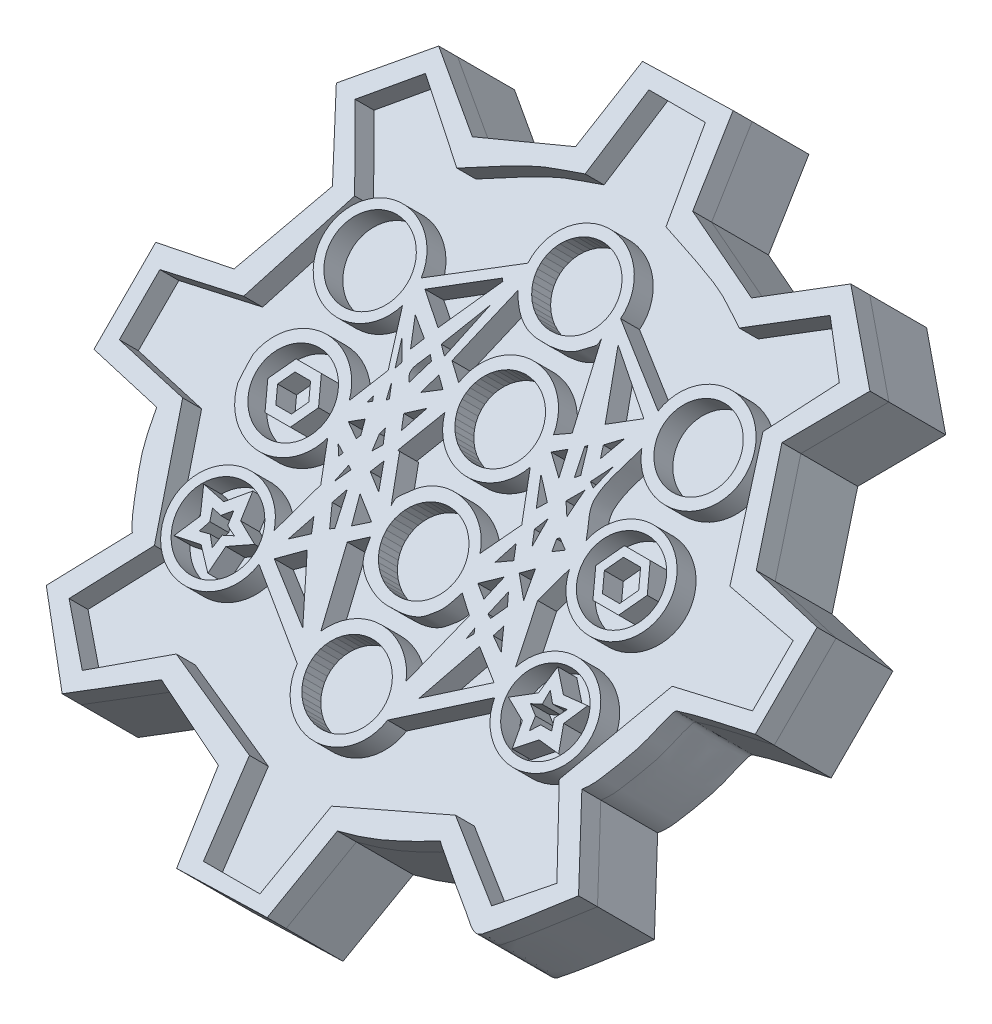
SolidWorks part; units mm, degrees
ref_plane "Front Plane" through (0, 0, 0) normal (0, 0, 1) x (1, 0, 0)
ref_plane "Top Plane" through (0, 0, 0) normal (0, 1, 0) x (1, 0, 0)
ref_plane "Right Plane" through (0, 0, 0) normal (1, 0, 0) x (0, 0, -1)
ref_plane "Plane2" through (0, -6.35, 0) normal (0, 1, 0) x (1, 0, 0)
sketch "Sketch2" plane through (0, -6.35, 0) normal (0, 1, 0) x (1, 0, 0)
  circle A0 centre (0, 0) radius 6.0325
  dimension "D1" = 12.065
ref_axis "Axis1" through (-6.2865, 0, 0) along (1, 0, 0)
ref_plane "Plane1" through (0, 0, 0) normal (0, 0.7071, 0.7071) x (1, 0, 0)
sketch "Sketch3" plane through (0, 0, 0) normal (0, 0.7071, 0.7071) x (1, 0, 0)
  line L0 (0, 0) -> (-25.4, 0) construction
  line L1 (-6.2865, 0) -> (6.2865, 0) construction
  line L2 (-25.4, -38.1) -> (-25.4, 38.1) construction
  circle A0 centre (0, 0) radius 12.7
  point P13 (-25.4, 0)
  point P15 (-20.32, 7.62)
  point P16 (-20.32, -7.62)
  point P17 (-20.32, -22.86)
  dimension "D1" = 25.4
  dimension "D4" = 25.4
  dimension "D5" = 76.2
extrude "Boss-Extrude1" add sketch "Sketch3" along normal blind 4.7625
extrude "Boss-Extrude2" add sketch "Sketch2" along normal up to surface and the other way blind 3.175 up to face at (0, -8.9803, 8.9803)
sketch "Sketch5" plane through (0, 3.3676, 3.3676) normal (0, 0.7071, 0.7071) x (1, 0, 0)
  line L0 (2.1384, 9.1764) -> (2.1514, 9.4647)
  line L1 (2.1514, 9.4647) -> (2.125, 9.7523)
  line L2 (2.125, 9.7523) -> (2.0598, 10.0341)
  line L3 (2.0598, 10.0341) -> (1.9568, 10.3051)
  line L4 (1.9568, 10.3051) -> (1.818, 10.5603)
  line L5 (1.818, 10.5603) -> (1.6457, 10.7953)
  line L6 (1.6457, 10.7953) -> (1.4431, 11.0059)
  line L7 (1.4431, 11.0059) -> (1.2138, 11.1882)
  line L8 (1.2138, 11.1882) -> (0.9619, 11.3391)
  line L9 (0.9619, 11.3391) -> (0.6918, 11.4559)
  line L10 (0.6918, 11.4559) -> (0.4085, 11.5365)
  line L11 (0.4085, 11.5365) -> (0.1168, 11.5794)
  line L12 (0.1168, 11.5794) -> (-0.1778, 11.5838)
  line L13 (-0.1778, 11.5838) -> (-0.4703, 11.5498)
  line L14 (-0.4703, 11.5498) -> (-0.7553, 11.4779)
  line L15 (-0.7553, 11.4779) -> (-1.0279, 11.3693)
  line L16 (-1.0279, 11.3693) -> (-1.283, 11.2261)
  line L17 (-1.283, 11.2261) -> (-1.5162, 11.0507)
  line L18 (-1.5162, 11.0507) -> (-1.7233, 10.8463)
  line L19 (-1.7233, 10.8463) -> (-1.9007, 10.6166)
  line L20 (-1.9007, 10.6166) -> (-2.045, 10.3657)
  line L21 (-2.045, 10.3657) -> (-2.1539, 10.098)
  line L22 (-2.1539, 10.098) -> (-2.2253, 9.8183)
  line L23 (-2.2253, 9.8183) -> (-2.2579, 9.5315)
  line L24 (-2.2579, 9.5315) -> (-2.2512, 9.243)
  line L25 (-2.2512, 9.243) -> (-2.2053, 8.9576)
  line L26 (-2.2053, 8.9576) -> (-2.121, 8.6806)
  line L27 (-2.121, 8.6806) -> (-1.9998, 8.417)
  line L28 (-1.9998, 8.417) -> (-1.8439, 8.1713)
  line L29 (-1.8439, 8.1713) -> (-1.6561, 7.948)
  line L30 (-1.6561, 7.948) -> (-1.4396, 7.7511)
  line L31 (-1.4396, 7.7511) -> (-1.1985, 7.5841)
  line L32 (-1.1985, 7.5841) -> (-0.9369, 7.45)
  line L33 (-0.9369, 7.45) -> (-0.6596, 7.3511)
  line L34 (-0.6596, 7.3511) -> (-0.3714, 7.2892)
  line L35 (-0.3714, 7.2892) -> (-0.0776, 7.2655)
  line L36 (-0.0776, 7.2655) -> (0.2166, 7.2803)
  line L37 (0.2166, 7.2803) -> (0.506, 7.3334)
  line L38 (0.506, 7.3334) -> (0.7854, 7.4239)
  line L39 (0.7854, 7.4239) -> (1.0498, 7.55)
  line L40 (1.0498, 7.55) -> (1.2946, 7.7097)
  line L41 (1.2946, 7.7097) -> (1.5152, 7.9)
  line L42 (1.5152, 7.9) -> (1.7079, 8.1175)
  line L43 (1.7079, 8.1175) -> (1.8691, 8.3584)
  line L44 (1.8691, 8.3584) -> (1.996, 8.6183)
  line L45 (1.996, 8.6183) -> (2.0863, 8.8926)
  line L46 (2.0863, 8.8926) -> (2.1384, 9.1764)
  line L47 (2.1553, 2.9225) -> (2.146, 3.2114)
  line L48 (2.146, 3.2114) -> (2.0975, 3.4967)
  line L49 (2.0975, 3.4967) -> (2.0105, 3.7731)
  line L50 (2.0105, 3.7731) -> (1.8868, 4.0357)
  line L51 (1.8868, 4.0357) -> (1.7284, 4.2799)
  line L52 (1.7284, 4.2799) -> (1.5383, 4.5013)
  line L53 (1.5383, 4.5013) -> (1.3198, 4.696)
  line L54 (1.3198, 4.696) -> (1.0768, 4.8604)
  line L55 (1.0768, 4.8604) -> (0.8136, 4.9916)
  line L56 (0.8136, 4.9916) -> (0.535, 5.0874)
  line L57 (0.535, 5.0874) -> (0.2459, 5.1459)
  line L58 (0.2459, 5.1459) -> (-0.0486, 5.1662)
  line L59 (-0.0486, 5.1662) -> (-0.3431, 5.1478)
  line L60 (-0.3431, 5.1478) -> (-0.6324, 5.0912)
  line L61 (-0.6324, 5.0912) -> (-0.9114, 4.9973)
  line L62 (-0.9114, 4.9973) -> (-1.1751, 4.8677)
  line L63 (-1.1751, 4.8677) -> (-1.4187, 4.7049)
  line L64 (-1.4187, 4.7049) -> (-1.638, 4.5117)
  line L65 (-1.638, 4.5117) -> (-1.8289, 4.2915)
  line L66 (-1.8289, 4.2915) -> (-1.9882, 4.0484)
  line L67 (-1.9882, 4.0484) -> (-2.1129, 3.7865)
  line L68 (-2.1129, 3.7865) -> (-2.2009, 3.5107)
  line L69 (-2.2009, 3.5107) -> (-2.2505, 3.2258)
  line L70 (-2.2505, 3.2258) -> (-2.2609, 2.9369)
  line L71 (-2.2609, 2.9369) -> (-2.2319, 2.6491)
  line L72 (-2.2319, 2.6491) -> (-2.164, 2.3677)
  line L73 (-2.164, 2.3677) -> (-2.0585, 2.0975)
  line L74 (-2.0585, 2.0975) -> (-1.9171, 1.8436)
  line L75 (-1.9171, 1.8436) -> (-1.7425, 1.6102)
  line L76 (-1.7425, 1.6102) -> (-1.5377, 1.4017)
  line L77 (-1.5377, 1.4017) -> (-1.3064, 1.2218)
  line L78 (-1.3064, 1.2218) -> (-1.0527, 1.0737)
  line L79 (-1.0527, 1.0737) -> (-0.7812, 0.9599)
  line L80 (-0.7812, 0.9599) -> (-0.4967, 0.8826)
  line L81 (-0.4967, 0.8826) -> (-0.2043, 0.8431)
  line L82 (-0.2043, 0.8431) -> (0.0908, 0.8421)
  line L83 (0.0908, 0.8421) -> (0.3834, 0.8797)
  line L84 (0.3834, 0.8797) -> (0.6682, 0.9552)
  line L85 (0.6682, 0.9552) -> (0.9401, 1.0671)
  line L86 (0.9401, 1.0671) -> (1.1944, 1.2137)
  line L87 (1.1944, 1.2137) -> (1.4263, 1.3921)
  line L88 (1.4263, 1.3921) -> (1.6319, 1.5992)
  line L89 (1.6319, 1.5992) -> (1.8074, 1.8314)
  line L90 (1.8074, 1.8314) -> (1.9497, 2.0845)
  line L91 (1.9497, 2.0845) -> (2.0563, 2.3539)
  line L92 (2.0563, 2.3539) -> (2.1252, 2.6349)
  line L93 (2.1252, 2.6349) -> (2.1553, 2.9225)
  line L94 (2.1447, -3.5357) -> (2.1432, -3.2468)
  line L95 (2.1432, -3.2468) -> (2.1025, -2.9605)
  line L96 (2.1025, -2.9605) -> (2.0232, -2.682)
  line L97 (2.0232, -2.682) -> (1.9066, -2.4162)
  line L98 (1.9066, -2.4162) -> (1.755, -2.1679)
  line L99 (1.755, -2.1679) -> (1.571, -1.9415)
  line L100 (1.571, -1.9415) -> (1.3579, -1.7411)
  line L101 (1.3579, -1.7411) -> (1.1195, -1.5702)
  line L102 (1.1195, -1.5702) -> (0.8601, -1.4319)
  line L103 (0.8601, -1.4319) -> (0.5842, -1.3286)
  line L104 (0.5842, -1.3286) -> (0.2968, -1.2622)
  line L105 (0.2968, -1.2622) -> (0.003, -1.2339)
  line L106 (0.003, -1.2339) -> (-0.2918, -1.2442)
  line L107 (-0.2918, -1.2442) -> (-0.5826, -1.2929)
  line L108 (-0.5826, -1.2929) -> (-0.864, -1.3791)
  line L109 (-0.864, -1.3791) -> (-1.1311, -1.5013)
  line L110 (-1.1311, -1.5013) -> (-1.379, -1.6573)
  line L111 (-1.379, -1.6573) -> (-1.6034, -1.8443)
  line L112 (-1.6034, -1.8443) -> (-1.8003, -2.059)
  line L113 (-1.8003, -2.059) -> (-1.9662, -2.2976)
  line L114 (-1.9662, -2.2976) -> (-2.098, -2.5558)
  line L115 (-2.098, -2.5558) -> (-2.1934, -2.8289)
  line L116 (-2.1934, -2.8289) -> (-2.2508, -3.1122)
  line L117 (-2.2508, -3.1122) -> (-2.2691, -3.4006)
  line L118 (-2.2691, -3.4006) -> (-2.248, -3.6888)
  line L119 (-2.248, -3.6888) -> (-2.1878, -3.9719)
  line L120 (-2.1878, -3.9719) -> (-2.0896, -4.2446)
  line L121 (-2.0896, -4.2446) -> (-1.9553, -4.5022)
  line L122 (-1.9553, -4.5022) -> (-1.7871, -4.7401)
  line L123 (-1.7871, -4.7401) -> (-1.5881, -4.954)
  line L124 (-1.5881, -4.954) -> (-1.3618, -5.1401)
  line L125 (-1.3618, -5.1401) -> (-1.1123, -5.295)
  line L126 (-1.1123, -5.295) -> (-0.8441, -5.4161)
  line L127 (-0.8441, -5.4161) -> (-0.5618, -5.5011)
  line L128 (-0.5618, -5.5011) -> (-0.2706, -5.5485)
  line L129 (-0.2706, -5.5485) -> (0.0244, -5.5576)
  line L130 (0.0244, -5.5576) -> (0.3179, -5.528)
  line L131 (0.3179, -5.528) -> (0.6046, -5.4604)
  line L132 (0.6046, -5.4604) -> (0.8794, -5.356)
  line L133 (0.8794, -5.356) -> (1.1375, -5.2166)
  line L134 (1.1375, -5.2166) -> (1.3742, -5.0447)
  line L135 (1.3742, -5.0447) -> (1.5854, -4.8434)
  line L136 (1.5854, -4.8434) -> (1.7671, -4.6162)
  line L137 (1.7671, -4.6162) -> (1.9163, -4.3673)
  line L138 (1.9163, -4.3673) -> (2.0302, -4.101)
  line L139 (2.0302, -4.101) -> (2.1067, -3.8222)
  line L140 (2.1067, -3.8222) -> (2.1447, -3.5357)
  line L141 (2.1098, -10.2575) -> (2.1477, -9.9761)
  line L142 (2.1477, -9.9761) -> (2.1479, -9.692)
  line L143 (2.1479, -9.692) -> (2.1103, -9.41)
  line L144 (2.1103, -9.41) -> (2.0357, -9.135)
  line L145 (2.0357, -9.135) -> (1.9252, -8.8716)
  line L146 (1.9252, -8.8716) -> (1.7807, -8.6245)
  line L147 (1.7807, -8.6245) -> (1.6048, -8.3977)
  line L148 (1.6048, -8.3977) -> (1.4005, -8.1951)
  line L149 (1.4005, -8.1951) -> (1.1711, -8.0204)
  line L150 (1.1711, -8.0204) -> (0.9208, -7.8763)
  line L151 (0.9208, -7.8763) -> (0.6537, -7.7655)
  line L152 (0.6537, -7.7655) -> (0.3744, -7.6897)
  line L153 (0.3744, -7.6897) -> (0.0877, -7.6504)
  line L154 (0.0877, -7.6504) -> (-0.2014, -7.6481)
  line L155 (-0.2014, -7.6481) -> (-0.4882, -7.6829)
  line L156 (-0.4882, -7.6829) -> (-0.7675, -7.7542)
  line L157 (-0.7675, -7.7542) -> (-1.0348, -7.8608)
  line L158 (-1.0348, -7.8608) -> (-1.2853, -8.0008)
  line L159 (-1.2853, -8.0008) -> (-1.5148, -8.172)
  line L160 (-1.5148, -8.172) -> (-1.7194, -8.3712)
  line L161 (-1.7194, -8.3712) -> (-1.8956, -8.5952)
  line L162 (-1.8956, -8.5952) -> (-2.0403, -8.8401)
  line L163 (-2.0403, -8.8401) -> (-2.1511, -9.1017)
  line L164 (-2.1511, -9.1017) -> (-2.2262, -9.3755)
  line L165 (-2.2262, -9.3755) -> (-2.2641, -9.6569)
  line L166 (-2.2641, -9.6569) -> (-2.2642, -9.941)
  line L167 (-2.2642, -9.941) -> (-2.2267, -10.223)
  line L168 (-2.2267, -10.223) -> (-2.152, -10.498)
  line L169 (-2.152, -10.498) -> (-2.0415, -10.7613)
  line L170 (-2.0415, -10.7613) -> (-1.897, -11.0085)
  line L171 (-1.897, -11.0085) -> (-1.7211, -11.2353)
  line L172 (-1.7211, -11.2353) -> (-1.5168, -11.4378)
  line L173 (-1.5168, -11.4378) -> (-1.2875, -11.6126)
  line L174 (-1.2875, -11.6126) -> (-1.0371, -11.7567)
  line L175 (-1.0371, -11.7567) -> (-0.77, -11.8675)
  line L176 (-0.77, -11.8675) -> (-0.4907, -11.9433)
  line L177 (-0.4907, -11.9433) -> (-0.2041, -11.9826)
  line L178 (-0.2041, -11.9826) -> (0.0851, -11.9849)
  line L179 (0.0851, -11.9849) -> (0.3718, -11.9501)
  line L180 (0.3718, -11.9501) -> (0.6512, -11.8788)
  line L181 (0.6512, -11.8788) -> (0.9184, -11.7722)
  line L182 (0.9184, -11.7722) -> (1.169, -11.6321)
  line L183 (1.169, -11.6321) -> (1.3985, -11.461)
  line L184 (1.3985, -11.461) -> (1.6031, -11.2618)
  line L185 (1.6031, -11.2618) -> (1.7793, -11.0378)
  line L186 (1.7793, -11.0378) -> (1.924, -10.7929)
  line L187 (1.924, -10.7929) -> (2.0348, -10.5313)
  line L188 (2.0348, -10.5313) -> (2.1098, -10.2575)
  line L189 (11.1815, -5.5544) -> (9.8248, -5.6673)
  line L190 (9.1225, -5.7799) -> (9.1225, -6.4565)
  line L191 (9.1225, -6.4565) -> (8.5826, -6.6798)
  line L192 (8.5826, -6.6798) -> (9.1225, -7.0175)
  line L193 (9.1225, -7.0175) -> (9.2346, -7.6897)
  line L194 (9.2346, -7.6897) -> (9.5792, -7.2361)
  line L195 (9.5792, -7.2361) -> (10.233, -7.2361)
  line L196 (10.233, -7.2361) -> (10.011, -6.6996)
  line L197 (10.011, -6.6996) -> (10.3747, -6.1182)
  line L198 (10.3747, -6.1182) -> (9.5792, -6.227)
  line L199 (9.5792, -6.227) -> (9.1225, -5.7799)
  line L200 (10.5709, -6.6996) -> (11.1815, -5.5544)
  line L201 (11.1233, -7.9115) -> (10.5709, -6.6996)
  line L202 (9.9061, -7.8107) -> (11.1233, -7.9115)
  line L203 (8.9329, -8.7049) -> (9.9061, -7.8107)
  line L204 (8.6664, -7.4675) -> (8.9329, -8.7049)
  line L205 (7.4397, -6.9096) -> (8.6664, -7.4675)
  line L206 (8.6664, -6.1182) -> (7.4397, -6.9096)
  line L207 (8.8526, -4.7674) -> (8.6664, -6.1182)
  line L208 (9.8248, -5.6673) -> (8.8526, -4.7674)
  line L209 (7.9446, -0.3005) -> (8.7074, -1.6217)
  line L210 (10.4872, -0.3005) -> (9.9787, 0.5803)
  line L211 (9.9787, 0.5803) -> (8.9617, 0.5803)
  line L212 (8.9617, 0.5803) -> (8.4532, -0.3005)
  line L213 (8.4532, -0.3005) -> (8.9617, -1.1812)
  line L214 (8.9617, -1.1812) -> (9.9787, -1.1812)
  line L215 (9.9787, -1.1812) -> (10.4872, -0.3005)
  line L216 (8.7074, 1.0207) -> (7.9446, -0.3005)
  line L217 (10.233, 1.0207) -> (8.7074, 1.0207)
  line L218 (10.9958, -0.3005) -> (10.233, 1.0207)
  line L219 (10.233, -1.6217) -> (10.9958, -0.3005)
  line L220 (8.7074, -1.6217) -> (10.233, -1.6217)
  line L221 (-11.4271, -0.3799) -> (-10.6764, -1.6802)
  line L222 (-9.0014, -0.3799) -> (-9.4635, 0.4205)
  line L223 (-9.4635, 0.4205) -> (-10.3877, 0.4205)
  line L224 (-10.3877, 0.4205) -> (-10.8498, -0.3799)
  line L225 (-10.8498, -0.3799) -> (-10.3877, -1.1803)
  line L226 (-10.3877, -1.1803) -> (-9.4635, -1.1803)
  line L227 (-9.4635, -1.1803) -> (-9.0014, -0.3799)
  line L228 (-10.6764, 0.9204) -> (-11.4271, -0.3799)
  line L229 (-9.1749, 0.9204) -> (-10.6764, 0.9204)
  line L230 (-8.4241, -0.3799) -> (-9.1749, 0.9204)
  line L231 (-9.1749, -1.6802) -> (-8.4241, -0.3799)
  line L232 (-10.6764, -1.6802) -> (-9.1749, -1.6802)
  line L233 (-9.9942, -7.2361) -> (-10.5615, -7.3583)
  line L234 (-11.5651, -5.5544) -> (-10.2232, -5.7799)
  line L235 (-10.2232, -5.7799) -> (-9.2055, -4.7798)
  line L236 (-9.2055, -4.7798) -> (-8.9824, -6.1183)
  line L237 (-8.9824, -6.1183) -> (-7.7542, -6.6768)
  line L238 (-7.7542, -6.6768) -> (-8.9824, -7.3583)
  line L239 (-8.9824, -7.3583) -> (-9.0939, -8.7049)
  line L240 (-9.0939, -8.7049) -> (-10.1253, -7.8107)
  line L241 (-10.1253, -7.8107) -> (-11.5651, -8.0507)
  line L242 (-11.5651, -8.0507) -> (-10.8942, -6.7924)
  line L243 (-10.8942, -6.7924) -> (-11.5651, -5.5544)
  line L244 (-9.5485, -7.6897) -> (-9.9942, -7.2361)
  line L245 (-9.4371, -7.0269) -> (-9.5485, -7.6897)
  line L246 (-8.8749, -6.7924) -> (-9.4371, -7.0269)
  line L247 (-9.4371, -6.5611) -> (-8.8749, -6.7924)
  line L248 (-9.5485, -5.8929) -> (-9.4371, -6.5611)
  line L249 (-10.0073, -6.3437) -> (-9.5485, -5.8929)
  line L250 (-10.5615, -6.2297) -> (-10.0073, -6.3437)
  line L251 (-10.3287, -6.7924) -> (-10.5615, -6.2297)
  line L252 (-10.5615, -7.3583) -> (-10.3287, -6.7924)
  line L253 (2.5066, 1.9018) -> (3.6134, -0.3799)
  line L254 (3.6134, -4.7674) -> (2.4884, -8.4799)
  line L255 (-3.6991, 4.1201) -> (-2.8364, 3.4604)
  line L256 (6.2009, 3.6701) -> (5.555, 2.634)
  line L257 (-6.5116, 3.8951) -> (-6.033, 2.6576)
  line L258 (5.5259, 2.2076) -> (4.9634, 1.4201)
  line L259 (-3.4238, 6.9255) -> (-4.5991, 4.493)
  line L260 (-3.4741, 8.0576) -> (-5.1616, 5.0201)
  line L261 (3.2759, 8.1701) -> (6.3134, 6.0326)
  line L262 (-6.5116, 5.0201) -> (-5.4991, 4.3451)
  line L263 (4.9634, 2.6576) -> (4.7384, 2.4326)
  line L264 (-3.9241, 3.3326) -> (-3.3616, 2.8826)
  line L265 (3.7259, 3.3326) -> (4.0634, 2.0951)
  line L266 (-5.8366, 2.0951) -> (-5.4991, 1.4201)
  line L267 (-3.5866, 1.8701) -> (-4.1491, 0.5201)
  line L268 (3.1634, 1.8701) -> (4.1759, 0.9701)
  line L269 (-6.2866, 1.1951) -> (-6.1741, 0.9701)
  line L270 (4.6259, 0.4076) -> (4.6259, -0.9424)
  line L271 (-4.5991, -0.3799) -> (-4.9366, -0.8299)
  line L272 (-5.8366, -0.4924) -> (-5.9491, -0.7174)
  line L273 (6.2009, -0.3799) -> (5.6384, -0.7174)
  line L274 (-4.1491, -0.9424) -> (-3.5866, -2.1799)
  line L275 (3.8384, -1.1674) -> (4.1759, -1.8424)
  line L276 (-6.6241, -1.2799) -> (-6.1741, -1.5049)
  line L277 (-5.6116, -1.8424) -> (-5.3866, -1.9549)
  line L278 (-4.3741, -2.6299) -> (-3.1366, -3.4174)
  line L279 (4.1759, -2.6299) -> (3.8384, -3.8674)
  line L280 (-4.5991, -4.4299) -> (-4.8241, -4.5424)
  line L281 (5.0759, -3.6424) -> (4.6259, -4.4299)
  line L282 (-5.8366, -4.4299) -> (-5.4991, -5.1049)
  line L283 (5.4134, -4.4299) -> (5.9759, -5.4424)
  line L284 (4.8509, -5.6674) -> (6.4259, -6.6799)
  line L285 (-5.2741, -5.7799) -> (-3.4741, -8.7049)
  line L286 (4.7384, -2.1799) -> (5.347, -1.6823)
  line L287 (-4.8241, 3.8951) -> (-4.5991, 3.6701)
  line L288 (2.7134, -4.0924) -> (3.6134, -4.7674)
  line L289 (-3.6991, -4.6549) -> (-2.7991, -3.9799)
  line L290 (-2.585, -8.443) -> (-3.6991, -4.6549)
  line L291 (3.5009, 4.0076) -> (2.7134, 3.5576)
  line L292 (2.3759, 8.0576) -> (3.5009, 4.0076)
  line L293 (-3.6991, 4.1201) -> (-2.5741, 8.0576)
  line L294 (5.555, 2.634) -> (5.8506, 2.4498)
  line L295 (5.8506, 2.4498) -> (6.2009, 3.6701)
  line L296 (-5.8854, 3.002) -> (-6.5116, 3.8951)
  line L297 (4.9634, 1.4201) -> (5.4134, 0.8576)
  line L298 (5.4134, 0.8576) -> (5.5259, 2.2076)
  line L299 (-4.5991, 4.493) -> (-4.1491, 4.1201)
  line L300 (-4.1491, 4.1201) -> (-3.4238, 6.9255)
  line L301 (-3.5866, 8.1701) -> (-3.4741, 8.0576)
  line L302 (-6.7366, 6.1451) -> (-3.5866, 8.1701)
  line L303 (-5.1616, 5.0201) -> (-6.7366, 6.1451)
  line L304 (4.7384, 5.0201) -> (3.2759, 8.1701)
  line L305 (6.3134, 6.0326) -> (4.7384, 5.0201)
  line L306 (-5.8366, 3.6701) -> (-6.5116, 5.0201)
  line L307 (-5.4991, 4.3451) -> (-5.8366, 3.6701)
  line L308 (5.1884, 4.2326) -> (5.9759, 4.9076)
  line L309 (5.4134, 3.6701) -> (5.1884, 4.2326)
  line L310 (4.5134, 3.8951) -> (4.9634, 2.6576)
  line L311 (4.4009, 3.7826) -> (4.5134, 3.8951)
  line L312 (4.7384, 2.4326) -> (4.4009, 3.7826)
  line L313 (-4.2616, 2.3201) -> (-3.9241, 3.3326)
  line L314 (-3.3616, 2.8826) -> (-4.2616, 2.3201)
  line L315 (3.0509, 2.8826) -> (3.7259, 3.3326)
  line L316 (4.0634, 2.0951) -> (3.0509, 2.8826)
  line L317 (-5.6116, 1.3076) -> (-5.8366, 2.0951)
  line L318 (-5.4991, 1.4201) -> (-5.6116, 1.3076)
  line L319 (-4.4866, 1.1951) -> (-3.5866, 1.8701)
  line L320 (-4.1491, 0.5201) -> (-4.4866, 1.1951)
  line L321 (3.8384, 0.5201) -> (3.1634, 1.8701)
  line L322 (4.1759, 0.9701) -> (3.8384, 0.5201)
  line L323 (-6.3991, 0.8576) -> (-6.2866, 1.1951)
  line L324 (-6.1741, 0.9701) -> (-6.3991, 0.8576)
  line L325 (4.2884, -0.2674) -> (4.6259, 0.4076)
  line L326 (4.6259, -0.9424) -> (4.2884, -0.2674)
  line L327 (-4.9366, 0.2951) -> (-4.5991, -0.3799)
  line L328 (-5.0491, -0.0424) -> (-4.9366, 0.2951)
  line L329 (-4.9366, -0.8299) -> (-5.0491, -0.0424)
  line L330 (-6.0616, 0.1826) -> (-5.8366, -0.4924)
  line L331 (-6.7366, -0.2674) -> (-6.0616, 0.1826)
  line L332 (-5.9491, -0.7174) -> (-6.7366, -0.2674)
  line L333 (5.6384, -0.0424) -> (6.2009, -0.3799)
  line L334 (5.5259, -0.1549) -> (5.6384, -0.0424)
  line L335 (5.6384, -0.7174) -> (5.5259, -0.1549)
  line L336 (-4.4866, -1.6174) -> (-4.1491, -0.9424)
  line L337 (-3.5866, -2.1799) -> (-4.4866, -1.6174)
  line L338 (3.3884, -2.2924) -> (3.8384, -1.1674)
  line L339 (4.1759, -1.8424) -> (3.3884, -2.2924)
  line L340 (-6.2866, -1.7299) -> (-6.6241, -1.2799)
  line L341 (-6.1741, -1.5049) -> (-6.2866, -1.7299)
  line L342 (-5.8366, -2.7424) -> (-5.6116, -1.8424)
  line L343 (-5.3866, -1.9549) -> (-5.8366, -2.7424)
  line L344 (-3.9241, -3.9799) -> (-4.3741, -2.6299)
  line L345 (-3.1366, -3.4174) -> (-3.9241, -3.9799)
  line L346 (3.1634, -3.4174) -> (4.1759, -2.6299)
  line L347 (3.8384, -3.8674) -> (3.1634, -3.4174)
  line L348 (-5.0491, -2.7424) -> (-4.5991, -4.4299)
  line L349 (-5.3866, -3.5299) -> (-5.0491, -2.7424)
  line L350 (-4.8241, -4.5424) -> (-5.3866, -3.5299)
  line L351 (4.7384, -3.0799) -> (5.0759, -3.6424)
  line L352 (4.4009, -4.3174) -> (4.7384, -3.0799)
  line L353 (4.6259, -4.4299) -> (4.4009, -4.3174)
  line L354 (-6.3991, -5.7799) -> (-5.8366, -4.4299)
  line L355 (-5.4991, -5.1049) -> (-6.3991, -5.7799)
  line L356 (5.1884, -4.9924) -> (5.4134, -4.4299)
  line L357 (5.9759, -5.4424) -> (5.1884, -4.9924)
  line L358 (4.0634, -5.6674) -> (4.1759, -5.1049)
  line L359 (4.2884, -5.3299) -> (4.0634, -5.6674)
  line L360 (3.5009, -8.8174) -> (4.8509, -5.6674)
  line L361 (6.4259, -6.6799) -> (3.5009, -8.8174)
  line L362 (-6.5116, -6.7924) -> (-5.2741, -5.7799)
  line L363 (-3.4741, -8.7049) -> (-6.5116, -6.7924)
  line L364 (5.6384, -3.0799) -> (4.7384, -2.1799)
  line L365 (5.347, -1.6823) -> (5.6384, -3.0799)
  line L366 (6.9884, -5.6673) -> (6.2574, -2.7867)
  line L367 (6.843, -7.2114) -> (2.6619, -10.2672)
  line L368 (-2.7991, -10.1154) -> (-7.0549, -7.3059)
  line L369 (-7.2401, -5.7799) -> (-6.3459, -3.1325)
  line L370 (-6.3459, -3.1325) -> (-7.2401, -1.2799)
  line L371 (-7.2401, 0.5201) -> (-6.2866, 2.4327)
  line L372 (-7.3159, 5.094) -> (-6.2866, 2.4327)
  line L373 (-7.1866, 6.4748) -> (-2.827, 9.2491)
  line L374 (2.7134, 9.1764) -> (6.751, 6.6092)
  line L375 (-4.5991, 3.6701) -> (-5.0491, 2.4326)
  line L376 (-3.8116, -0.2674) -> (-2.6866, 2.0951)
  line L377 (-3.6991, -0.2674) -> (-3.8116, -0.2674)
  line L378 (-2.6866, -2.4049) -> (-3.6991, -0.2674)
  line L379 (3.6134, -0.3799) -> (2.4884, -2.2924)
  line L380 (5.9759, 4.9076) -> (5.4134, 3.6701)
  line L381 (4.1759, -5.1049) -> (4.2884, -5.3299)
  line L382 (6.2574, -2.7867) -> (6.868, -0.979)
  line L383 (-6.033, 2.6576) -> (-5.8854, 3.002)
  line L384 (-12.2491, 8.0576) -> (-14.6116, 2.0951)
  line L385 (-19.014, 1.3076) -> (-14.6116, 2.0951)
  line L386 (-12.1792, -8.8174) -> (-14.7114, -2.8713)
  line L387 (-12.1792, -14.8613) -> (-14.6116, -12.5299)
  line L388 (-14.7114, 11.5722) -> (-12.2491, 8.0576)
  line L389 (-8.4241, -12.2962) -> (-2.5741, -14.4424)
  line L390 (-1.8991, -19.2478) -> (-2.5741, -14.4424)
  line L391 (-1.8991, -19.2478) -> (1.4449, -19.2478)
  line L392 (1.4449, -19.2478) -> (2.3759, -14.5643)
  line L393 (-19.014, -2.0891) -> (-14.7114, -2.8713)
  line L394 (8.1134, -12.2962) -> (12.0509, -14.8312)
  line L395 (14.3676, -12.6424) -> (12.0509, -14.8312)
  line L396 (11.804, -8.8174) -> (14.3676, -12.6424)
  line L397 (-12.1792, -14.8613) -> (-8.4241, -12.2962)
  line L398 (18.6402, -2.2924) -> (14.4368, -3.0799)
  line L399 (18.6402, 1.1109) -> (18.6402, -2.2924)
  line L400 (14.4368, 1.7576) -> (18.6402, 1.1109)
  line L401 (-19.014, -2.0891) -> (-19.014, 1.3076)
  line L402 (14.0759, 11.4326) -> (11.9384, 8.0576)
  line L403 (11.9384, 13.6826) -> (14.0759, 11.4326)
  line L404 (-14.6116, -12.5299) -> (-12.1792, -8.8174)
  line L405 (1.4449, 18.0701) -> (2.3759, 13.4576)
  line L406 (-1.8991, 18.0701) -> (1.4449, 18.0701)
  line L407 (-2.5741, 13.6826) -> (-1.8991, 18.0701)
  line L408 (-12.2491, 13.9853) -> (-8.4241, 11.2076)
  line L409 (2.3759, -19.9549) -> (3.2759, -15.3424)
  line L410 (2.3759, -19.9549) -> (-2.9116, -20.0674)
  line L411 (-3.6991, -15.4549) -> (-2.9116, -20.0674)
  line L412 (14.4368, -3.0799) -> (11.804, -8.8174)
  line L413 (-12.4741, -16.1299) -> (-8.4241, -13.5424)
  line L414 (-15.9616, -12.5299) -> (-12.4741, -16.1299)
  line L415 (-13.4866, -8.8174) -> (-15.9616, -12.5299)
  line L416 (-19.8991, -2.9674) -> (-15.6241, -3.7549)
  line L417 (-19.8991, -2.9674) -> (-19.8991, 2.2076)
  line L418 (-15.7366, 2.8826) -> (-19.8991, 2.2076)
  line L419 (-13.4866, 7.9451) -> (-15.7366, 2.8826)
  line L420 (-15.9616, 11.7701) -> (-13.4866, 7.9451)
  line L421 (-12.3616, 15.2576) -> (-15.9616, 11.7701)
  line L422 (-8.5366, 12.6701) -> (-12.3616, 15.2576)
  line L423 (-3.6991, 14.4701) -> (-8.5366, 12.6701)
  line L424 (-2.9116, 18.9701) -> (-3.6991, 14.4701)
  line L425 (2.3759, -14.5643) -> (8.1134, -12.2962)
  line L426 (3.1634, 14.5826) -> (2.3759, 19.0826)
  line L427 (8.0009, 12.6701) -> (3.1634, 14.5826)
  line L428 (12.0509, 15.2576) -> (8.0009, 12.6701)
  line L429 (15.6509, 11.7701) -> (12.0509, 15.2576)
  line L430 (13.0634, 8.0576) -> (15.6509, 11.7701)
  line L431 (15.2009, 2.8826) -> (13.0634, 8.0576)
  line L432 (19.3634, 2.0951) -> (15.2009, 2.8826)
  line L433 (19.3634, 2.0951) -> (19.3634, -3.0799)
  line L434 (15.6509, -12.6424) -> (13.0634, -8.7049)
  line L435 (8.2259, 11.3201) -> (11.9384, 13.6826)
  line L436 (-14.7114, 11.5722) -> (-12.2491, 13.9853)
  line L437 (11.9384, 8.0576) -> (14.4368, 1.7576)
  line L438 (-8.4241, -13.5424) -> (-3.6991, -15.4549)
  line L439 (-2.9116, 18.9701) -> (2.3759, 19.0826)
  circle A0 centre (9.4909, 6.1241) radius 2.1625
  circle A1 centre (-9.9256, -0.3799) radius 2.1919
  circle A2 centre (9.4702, -0.3005) radius 2.185
  circle A3 centre (-9.7958, -6.8643) radius 2.2672
  circle A4 centre (-9.9039, 6.0327) radius 2.2368
  circle A5 centre (9.4702, -6.6798) radius 2.1642
  arc A6 (2.4884, -8.4799) -> (-2.585, -8.443) centre (-0.0582, -9.8165) ccw
  arc A7 (2.7134, 3.5576) -> (-2.8364, 3.4604) centre (-0.0527, 3.002) ccw
  arc A8 (6.843, -7.2114) -> (6.9884, -5.6673) centre (9.4702, -6.6798) ccw
  arc A9 (-2.7991, -10.1154) -> (2.6619, -10.2672) centre (-0.0582, -9.8165) ccw
  arc A10 (-7.2401, -5.7799) -> (-7.0549, -7.3059) centre (-9.7958, -6.8643) ccw
  arc A11 (-7.2401, 0.5201) -> (-7.2401, -1.2799) centre (-9.9256, -0.3799) ccw
  arc A12 (-7.1866, 6.4748) -> (-7.3159, 5.094) centre (-9.9039, 6.0327) ccw
  arc A13 (2.7134, 9.1764) -> (-2.827, 9.2491) centre (-0.054, 9.426) ccw
  arc A14 (6.9884, 4.9077) -> (6.751, 6.6092) centre (9.4909, 6.1241) ccw
  arc A15 (6.868, -0.979) -> (6.8759, 0.4077) centre (9.4702, -0.3005) ccw
  arc A16 (-2.6866, 2.0951) -> (2.5066, 1.9018) centre (-0.0527, 3.002) ccw
  spline S0 degree 3 poles (-2.7991, -3.9799) (-2.7241, -4.2799) (-2.7021, -4.5984) (-2.5741, -4.8799) (-2.2447, -5.6045) (-1.0499, -6.1174) (-0.3241, -6.1174) (0.2812, -6.1174) (1.1746, -6.141) (1.7009, -5.6674) (2.4016, -5.0368) (2.372, -4.889) (2.7134, -4.0924) knots 0 0 0 0 1 1 1 2 2 2 3 3 3 4 4 4 4
  spline S1 degree 3 poles (-2.5741, 8.0576) (-2.1046, 7.3533) (-1.4724, 6.7846) (-0.5491, 6.7076) (0.0361, 6.6588) (1.1397, 6.6526) (1.7009, 7.1576) (2.4003, 7.7871) (2.3759, 7.6196) (2.3759, 8.0576) knots 0 0 0 0 1 1 1 2 2 2 3 3 3 3
  spline S2 degree 3 poles (6.8759, 0.4077) (6.6466, 0.9732) (6.1729, 1.4942) (6.1881, 2.1043) (6.2124, 3.0758) (6.7216, 3.9732) (6.9884, 4.9077) knots 0 0 0 0 1 1 1 2 2 2 2
  spline S3 degree 3 poles (-5.0491, 2.4326) (-5.5341, 2.9176) (-5.0848, 3.3086) (-4.8241, 3.8951) knots 0 0 0 0 1 1 1 1
  spline S4 degree 3 poles (2.4884, -2.2924) (1.7998, -0.5709) (-0.8003, 0.0518) (-2.1241, -1.3924) (-2.7065, -2.0277) (-2.6866, -1.97) (-2.6866, -2.4049) knots 0 0 0 0 1 1 1 2 2 2 2
  spline S5 degree 3 poles (8.1134, -13.5424) (8.1509, -13.5799) (8.1823, -13.6247) (8.2259, -13.6549) (9.106, -14.2642) (10.1409, -14.984) (11.0384, -15.5674) (11.335, -15.7602) (11.6028, -16.018) (11.9384, -16.1299) (12.0851, -16.1788) (12.2757, -16.1233) (12.3884, -16.0174) (13.5288, -14.9461) (14.5634, -13.7674) (15.6509, -12.6424) knots 0 0 0 0 1 1 1 2 2 2 3 3 3 4 4 4 5 5 5 5
  spline S6 degree 3 poles (2.3759, 13.4576) (3.6509, 13.0826) (4.9526, 12.7887) (6.2009, 12.3326) (6.9097, 12.0736) (7.5509, 11.6576) (8.2259, 11.3201) knots 0 0 0 0 1 1 1 2 2 2 2
  spline S7 degree 3 poles (-8.4241, 11.2076) (-7.2991, 11.7701) (-6.2075, 12.405) (-5.0491, 12.8951) (-4.2518, 13.2324) (-3.3991, 13.4201) (-2.5741, 13.6826) knots 0 0 0 0 1 1 1 2 2 2 2
  spline S8 degree 3 poles (3.2759, -15.3424) (5.2131, -14.9549) (6.3651, -14.4165) (8.1134, -13.5424) knots 0 0 0 0 1 1 1 1
  spline S9 degree 3 poles (-15.6241, -3.7549) (-15.432, -4.7154) (-15.1791, -5.7143) (-14.7241, -6.5674) (-14.6049, -6.791) (-13.9234, -8.3806) (-13.4866, -8.8174) knots 0 0 0 0 1 1 1 2 2 2 2
  spline S10 degree 3 poles (13.0634, -8.7049) (13.291, -8.4772) (13.4867, -8.1958) (13.6259, -7.9174) (13.941, -7.2872) (14.2676, -6.6604) (14.5259, -6.0049) (14.7563, -5.42) (14.8711, -4.7947) (15.0884, -4.2049) (15.1351, -4.078) (15.1826, -3.9018) (15.3134, -3.8674) (16.6434, -3.5174) (18.0134, -3.3424) (19.3634, -3.0799) knots 0 0 0 0 1 1 1 2 2 2 3 3 3 4 4 4 5 5 5 5
  circle M1 centre (0, 0) radius 12.7
extrude "Boss-Extrude3" add sketch "Sketch5" against normal blind 4.7625 contours L422 L421 L420 L419 L418 L417 L416 S9 L415 L414 L413 L438 L411 L410 L409 S8 S5 L434 S10 L433 L432 L431 L430 L429 L428 L427 L426 L439 L424 L423
extrude "Boss-Extrude4" add sketch "Sketch5<3>" along normal blind 1.5875 separate body contours A12 A4 M1 | A15 S2 A14 A0 L374 A13 L373 A12 A4 L372 L371 A11 L370 L369 A10 A3 L368 A9 L367 A8 A5 L366 L382 A2 A1 L383 L257 L296 L300 L299 L259 L298 M1 | L221 L232 L231 L230 L229 L228 L227 L226 L225 L224 L223 L222 | L434 S10 L433 L432 L431 L430 L429 L428 L427 L426 L439 L424 L423 L422 L421 L420 L419 L418 L417 L416 S9 L415 L414 L413 L438 L411 L410 L409 S8 S5 L408 S7 L407 L406 L405 S6 L435 L403 L402 L437 L400 L399 L398 L412 L396 L395 L394 L425 L392 L391 | L252 L251 L250 L249 L248 L247 L246 L245 L244 L233 L240 L239 L238 L237 L236 L235 L234 M1 | A10 A3 M1 | L189 L208 L207 L206 L205 L204 L203 L202 L201 L200 L199 L198 L197 L196 L195 L194 L193 L192 L191 L190 M1 | A8 A5 M1 | L209 L220 L219 L218 L217 L216 L215 L214 L213 L212 L211 L210 | A14 A0 M1 | L233 L252 L234 L243 L242 L241 L240 M1 | L202 L201 M1 region at (10.8283, -0.9468, 7.682) region at (10.6023, -1.9687, 8.7039) region at (11.5563, -0.4494, 7.1846) region at (7.4148, -0.3306, 7.0658) region at (-12.0184, -2.5875, 9.3227) region at (11.7272, 6.9118, -0.1766) region at (-10.0331, -2.0761, 8.8113) region at (-10.8527, -1.8109, 8.5461) region at (-9.4938, 9.3929, -2.6577) region at (8.3609, 3.608, 3.1272) region at (-11.0173, 3.5447, 3.1905) region at (-0.2797, -10.3904, 17.1256)
sketch "Sketch5<3>" plane through (0, 3.3676, 3.3676) normal (0, 0.7071, 0.7071) x (1, 0, 0) same geometry as "Sketch5"
sketch "Sketch6" plane through (0, 0, 0) normal (0, -0.7071, -0.7071) x (1, 0, 0)
  circle A0 centre (0, -12.7) radius 3
  dimension "D1" = 6
  dimension "D2" = 12.7
extrude "Cut-Extrude1" cut sketch "Sketch6" against normal blind 3
